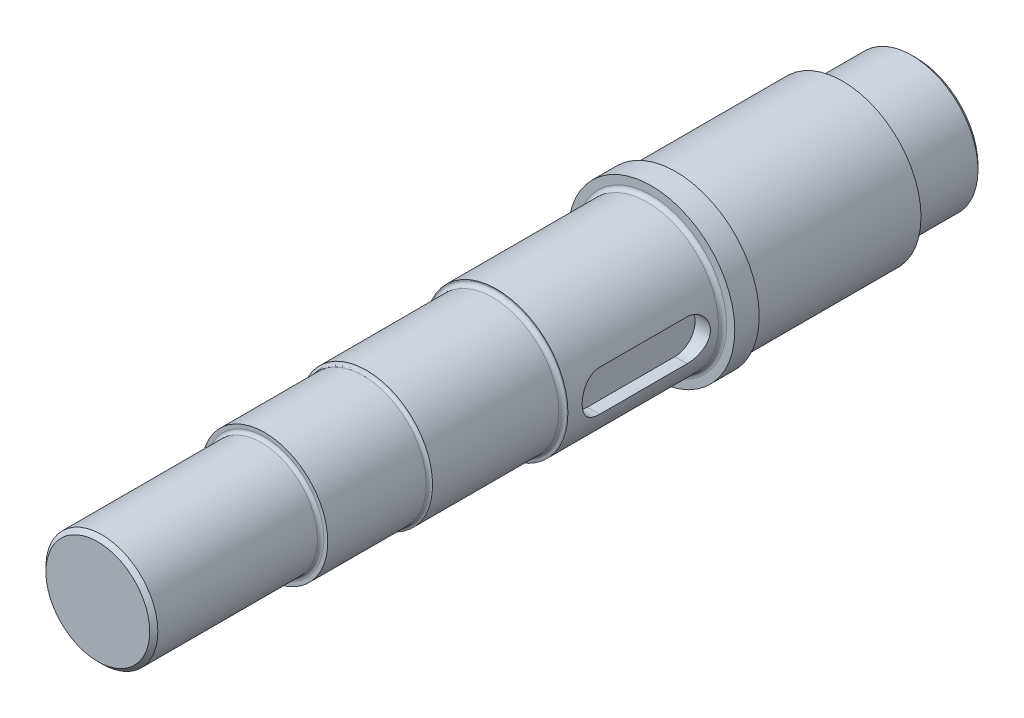
SolidWorks part; units mm, degrees
ref_plane "前视基准面" through (0, 0, 0) normal (0, 0, 1) x (1, 0, 0)
ref_plane "上视基准面" through (0, 0, 0) normal (0, 1, 0) x (1, 0, 0)
ref_plane "右视基准面" through (0, 0, 0) normal (1, 0, 0) x (0, 0, -1)
sketch "草图1" plane through (0, 0, 0) normal (0, 0, 1) x (1, 0, 0)
  circle A0 centre (0, 0) radius 32.5
  dimension "D1" = 65
extrude "凸台-拉伸1" add sketch "草图1" along normal blind 36
sketch "草图2" plane through (0, 0, 36) normal (0, 0, 1) x (1, 0, 0)
  circle A0 centre (0, 0) radius 38.5
  dimension "D1" = 77
extrude "凸台-拉伸2" add sketch "草图2" along normal blind 82
sketch "草图3" plane through (0, 0, 118) normal (0, 0, 1) x (1, 0, 0)
  circle A0 centre (0, 0) radius 41
  dimension "D1" = 82
extrude "凸台-拉伸3" add sketch "草图3" along normal blind 12
sketch "草图4" plane through (0, 0, 130) normal (0, 0, 1) x (1, 0, 0)
  circle A0 centre (0, 0) radius 35
  dimension "D1" = 70
extrude "凸台-拉伸4" add sketch "草图4" along normal blind 76
sketch "草图5" plane through (0, 0, 206) normal (0, 0, 1) x (1, 0, 0)
  circle A0 centre (0, 0) radius 32.5
  dimension "D1" = 65
extrude "凸台-拉伸5" add sketch "草图5" along normal blind 64
sketch "草图6" plane through (0, 0, 270) normal (0, 0, 1) x (1, 0, 0)
  circle A0 centre (0, 0) radius 31
  dimension "D1" = 62
extrude "凸台-拉伸6" add sketch "草图6" along normal blind 50
sketch "草图7" plane through (0, 0, 320) normal (0, 0, 1) x (1, 0, 0)
  circle A0 centre (0, 0) radius 27.5
  dimension "D1" = 55
extrude "凸台-拉伸7" add sketch "草图7" along normal blind 82
fillet "圆角1" radius 2 2 edges at (32.5, 0, 206) (35, 0, 130)
fillet "圆角2" radius 1.6 2 edges at (27.5, 0, 320) (31, 0, 270)
chamfer "倒角1" distance 2 angle 45 2 edges at (32.5, 0, 0) (27.5, 0, 402)
ref_plane "基准面1" through (27.5, 0, 0) normal (1, 0, 0) x (0, 0, -1)
sketch "草图8" plane through (27.5, 0, 0) normal (1, 0, 0) x (0, 0, -1)
  line L0 (-202.5, 0) -> (-135.849, 0) construction
  line L1 (-130, 37) -> (-130, -37) construction
  line L2 (-189, 10) -> (-146, 10)
  line L4 (-189, -10) -> (-146, -10)
  arc A0 (-146, -10) -> (-146, 10) centre (-146, 0) ccw
  arc A1 (-189, 10) -> (-189, -10) centre (-189, 0) ccw
  dimension "D4" = 20
  dimension "D5" = 20
  dimension "D1" = 20
  dimension "D2" = 10
  dimension "D3" = 43
  dimension "D6" = 16
extrude "切除-拉伸1" cut sketch "草图8" along normal blind 29
